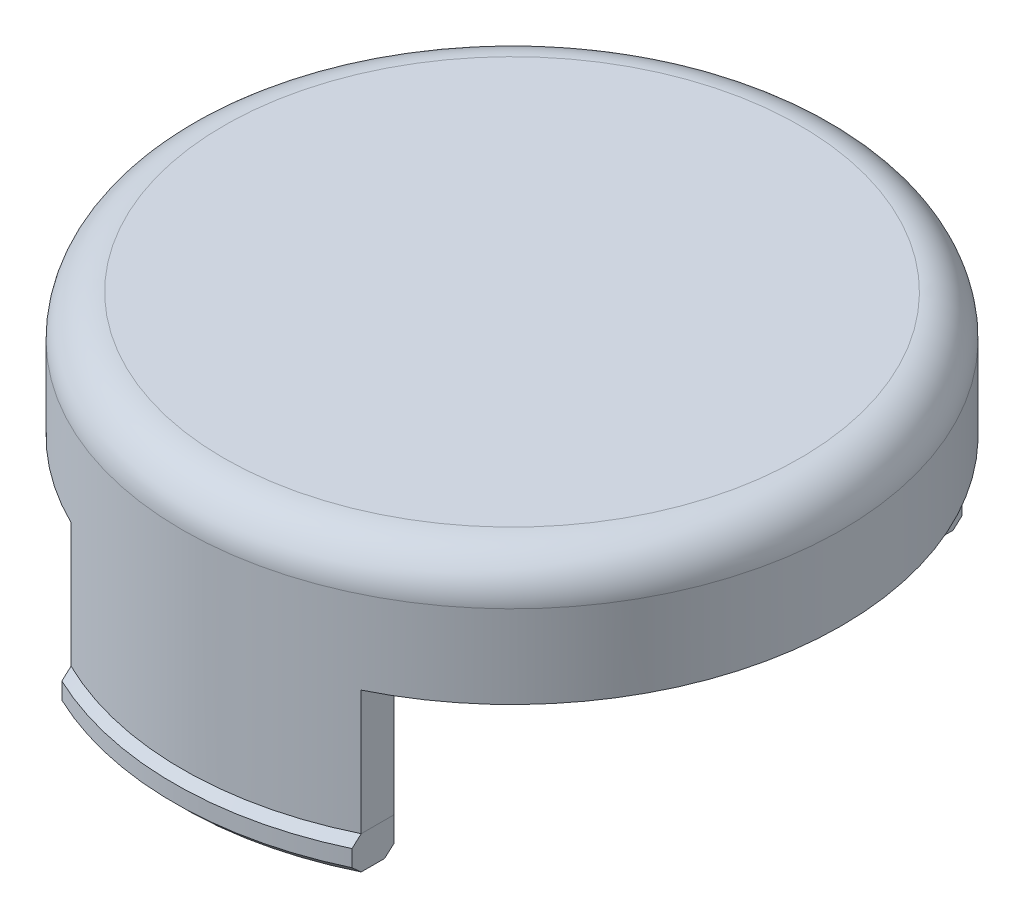
SolidWorks part; units mm, degrees
ref_plane "前视基准面" through (0, 0, 0) normal (0, 0, 1) x (1, 0, 0)
ref_plane "上视基准面" through (0, 0, 0) normal (0, 1, 0) x (1, 0, 0)
ref_plane "右视基准面" through (0, 0, 0) normal (1, 0, 0) x (0, 0, -1)
sketch "草图2" plane through (0, 0, 0) normal (0, 1, 0) x (1, 0, 0)
  circle A0 centre (0, 0) radius 7.95
  dimension "D1" = 15.9
extrude "凸台-拉伸1" add sketch "草图2" along normal blind 4
sketch "草图4" plane through (0, 0, 0) normal (0, -1, 0) x (1, 0, 0)
  circle A2 centre (0, 0) radius 8.15
  dimension "D1" = 16.3
extrude "凸台-拉伸2" add sketch "草图4" along normal blind 0.8 separate body
sketch "草图3" plane through (0, -0.8, 0) normal (0, -1, 0) x (1, 0, 0)
  circle A0 centre (0, 0) radius 7.25
  dimension "D1" = 14.5
extrude "切除-拉伸2" cut sketch "草图3" against normal blind 3.8
chamfer "倒角2" distance 0.2 angle 45 3 edges at (0, -0.8, -7.25) (0, -0.8, -8.15) (0, 0, -8.15)
sketch "草图5" plane through (0, 0, 0) normal (0, 0, 1) x (1, 0, 0)
  line L1 (-3.5, 3) -> (-10, 3)
  line L2 (-3.5, 3) -> (-3.5, -5)
  line L3 (-3.5, -5) -> (-10, -5)
  line L4 (-10, 3) -> (-10, -5)
  line L5 (-10, 1.1716) -> (-10, -1) construction
  line L6 (3.5, 3) -> (10, 3)
  line L7 (3.5, 3) -> (3.5, -5)
  line L8 (3.5, -5) -> (10, -5)
  line L9 (10, 3) -> (10, -5)
  line L10 (10, -1) -> (10, 1.1716) construction
  line L12 (7.95, 4) -> (-7.95, 4) construction
  dimension "D1" = 6.5
  dimension "D2" = 6.5
  dimension "D3" = 8
  dimension "D4" = 1
extrude "切除-拉伸3" cut sketch "草图5" against normal through all and the other way through all
sketch "草图6" plane through (0, 4, 0) normal (0, 1, 0) x (1, 0, 0)
  circle A1 centre (0, 0) radius 7.95
  circle A2 centre (0, 0) radius 7.95
  dimension "D1" = 0
extrude "凸台-拉伸3" add sketch "草图6" along normal blind 2
fillet "圆角1" radius 1 1 edges at (0, 6, 7.95)
sketch "草图7" plane through (0, 3, 0) normal (0, -1, 0) x (1, 0, 0)
  circle A0 centre (0, 0) radius 6.5
  dimension "D1" = 13
extrude "切除-拉伸4" cut sketch "草图7" against normal blind 1
